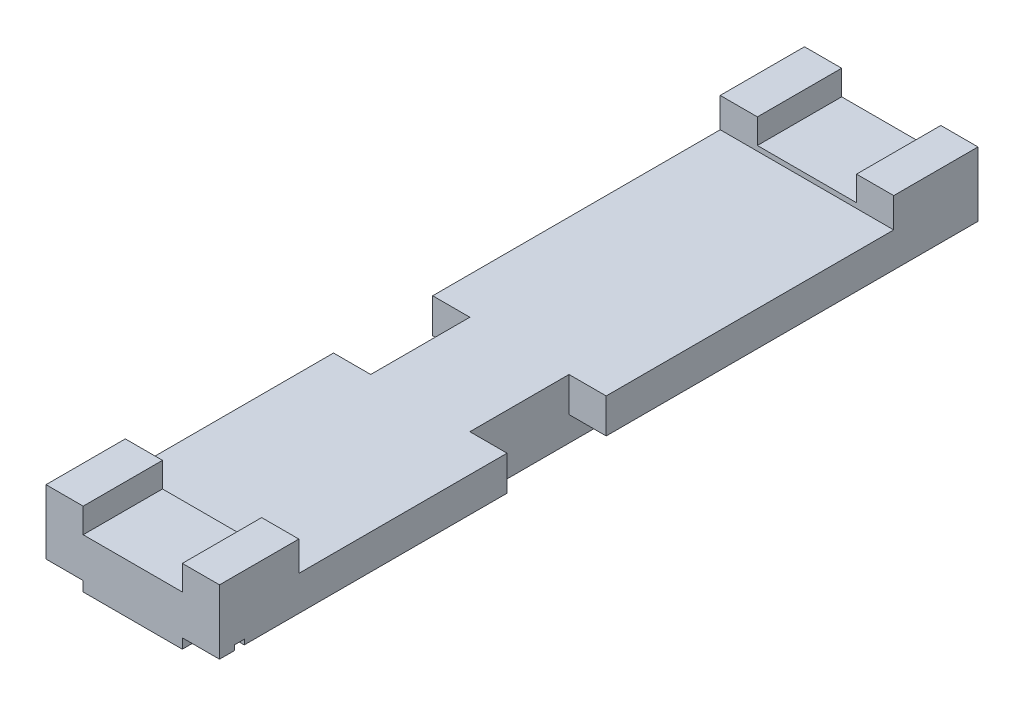
SolidWorks part; units mm, degrees
ref_plane "Front Plane" through (0, 0, 0) normal (0, 0, 1) x (1, 0, 0)
ref_plane "Top Plane" through (0, 0, 0) normal (0, 1, 0) x (1, 0, 0)
ref_plane "Right Plane" through (0, 0, 0) normal (1, 0, 0) x (0, 0, -1)
sketch "Sketch2" plane through (0, 0, 0) normal (0, 1, 0) x (1, 0, 0)
  line L0 (0, 0) -> (0, 15.3) construction
  line L2 (-1.75, 0) -> (1.75, 0)
  line L3 (-1.75, 0) -> (-1.75, 15.3)
  line L4 (-1.75, 15.3) -> (1.75, 15.3)
  line L5 (1.75, 0) -> (1.75, 15.3)
  dimension "D1" = 3.5
  dimension "D2" = 15.3
extrude "Boss-Extrude1" add sketch "Sketch2" along normal blind 1.8 contours L2 L5 L4 L3
sketch "Sketch3" plane through (1.75, 0, 0) normal (1, 0, 0) x (0, 0, -1)
  line L0 (0, 1.8) -> (15.3, 1.8) construction
  line L1 (1.6, 1.8) -> (13.6, 1.8)
  line L2 (1.6, 1.8) -> (1.6, 1.2)
  line L3 (1.6, 1.2) -> (13.6, 1.2)
  line L4 (13.6, 1.8) -> (13.6, 1.2)
  line L5 (0, 1.8) -> (0, 0) construction
  dimension "D1" = 1.6
  dimension "D2" = 12
  dimension "D3" = 0.6
extrude "Cut-Extrude1" cut sketch "Sketch3" against normal through all
sketch "Sketch4" plane through (1.75, 0, 0) normal (1, 0, 0) x (0, 0, -1)
  line L0 (0, 1.8) -> (0, 0) construction
  line L1 (0, 0.3) -> (2.3, 0.3)
  line L2 (0, 0.3) -> (0, 0)
  line L3 (0, 0) -> (2.3, 0)
  line L4 (2.3, 0.3) -> (2.3, 0)
  line L5 (0, 0) -> (15.3, 0) construction
  line L6 (13.6, 1.8) -> (15.3, 1.8) construction
  line L7 (15.3, 0) -> (13, 0)
  line L8 (15.3, 0) -> (15.3, 0.3)
  line L9 (15.3, 0.3) -> (13, 0.3)
  line L10 (13, 0) -> (13, 0.3)
  dimension "D1" = 2.3
  dimension "D2" = 2.3
  dimension "D3" = 1.5
extrude "Cut-Extrude2" cut sketch "Sketch4" against normal through all
sketch "Sketch5" plane through (0, 1.2, 0) normal (0, 1, 0) x (1, 0, 0)
  line L0 (0, 0) -> (0, 15.3) construction
  line L1 (-1.75, 0) -> (1.75, 0) construction
  line L2 (-1.75, 15.3) -> (1.75, 15.3) construction
  line L3 (-1.75, 1.6) -> (-1.75, 13.6) construction
  line L4 (-1.75, 7.8) -> (-1, 7.8)
  line L5 (-1.75, 7.8) -> (-1.75, 5.8)
  line L6 (-1.75, 5.8) -> (-1, 5.8)
  line L7 (-1, 7.8) -> (-1, 5.8)
  line L8 (1, 7.8) -> (1, 5.8)
  line L9 (1.75, 5.8) -> (1, 5.8)
  line L10 (1.75, 7.8) -> (1.75, 5.8)
  line L11 (1.75, 7.8) -> (1, 7.8)
  dimension "D1" = 5.8
  dimension "D2" = 2
  dimension "D3" = 2
extrude "Cut-Extrude3" cut sketch "Sketch5" against normal through all
sketch "Sketch8" plane through (0, 0, 0) normal (0, 0, 1) x (1, 0, 0)
  line L0 (0, 0) -> (0, 1.8) construction
  line L1 (-1.75, 0) -> (1.75, 0) construction
  line L2 (-1.75, 1.8) -> (1.75, 1.8) construction
  line L4 (-1, 1.8) -> (1, 1.8)
  line L5 (-1, 1.8) -> (-1, 1.3)
  line L6 (-1, 1.3) -> (1, 1.3)
  line L7 (1, 1.8) -> (1, 1.3)
  dimension "D1" = 0.5
  dimension "D2" = 2
extrude "Cut-Extrude5" cut sketch "Sketch8" against normal through all
sketch "Sketch9" plane through (0, 0, 0) normal (0, 0, 1) x (1, 0, 0)
  line L0 (0, 0) -> (0, 1.3) construction
  line L1 (-1, 1.3) -> (1, 1.3) construction
  line L2 (-1.75, 1.8) -> (-1, 1.8) construction
  line L3 (-1.75, 0) -> (-1, 0)
  line L4 (-1.75, 0) -> (-1.75, 0.5)
  line L5 (-1.75, 0.5) -> (-1, 0.5)
  line L6 (-1, 0) -> (-1, 0.5)
  line L7 (1, 0) -> (1, 0.5)
  line L8 (1.75, 0.5) -> (1, 0.5)
  line L9 (1.75, 0) -> (1.75, 0.5)
  line L10 (1.75, 0) -> (1, 0)
  dimension "D1" = 1.3
  dimension "D2" = 2
extrude "Cut-Extrude6" cut sketch "Sketch9" against normal through all
sketch "Sketch10" plane through (1.75, 0, 0) normal (1, 0, 0) x (0, 0, -1)
  line L0 (2.3, 0.3) -> (0, 0.3) construction
  line L1 (0.3, 0.6) -> (0.5, 0.6)
  line L2 (0.3, 0.6) -> (0.3, 0.3)
  line L3 (0.3, 0.3) -> (0.5, 0.3)
  line L4 (0.5, 0.6) -> (0.5, 0.3)
  line L5 (0, 1.8) -> (0, 0.5) construction
  dimension "D1" = 0.3
  dimension "D2" = 0.3
  dimension "D3" = 0.2
extrude "Cut-Extrude7" cut sketch "Sketch10" against normal through all
